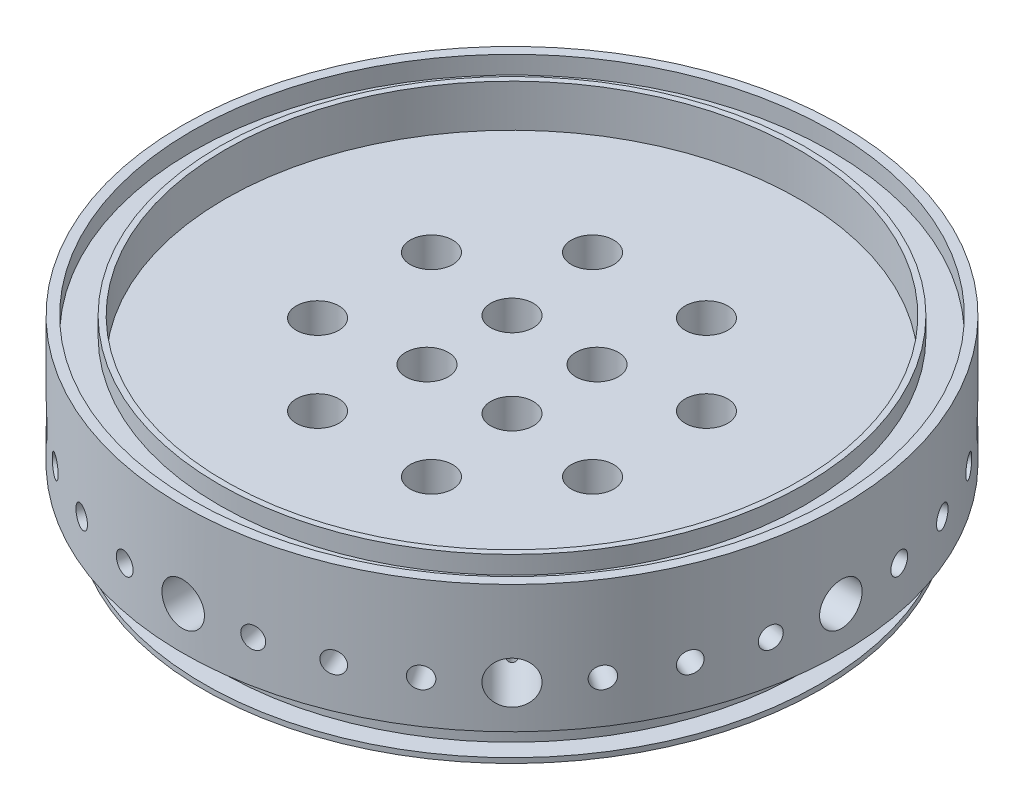
SolidWorks part; units mm, degrees
material "6061-T4 (SS)"
ref_plane "Front Plane" through (0, 0, 0) normal (0, 0, 1) x (1, 0, 0)
ref_plane "Top Plane" through (0, 0, 0) normal (0, 1, 0) x (1, 0, 0)
ref_plane "Right Plane" through (0, 0, 0) normal (1, 0, 0) x (0, 0, -1)
ref_axis "Axis1" through (0, -42.3, 0) along (0, 1, 0)
sketch "Sketch1" plane through (0, 0, 0) normal (0, 0, 1) x (1, 0, 0)
  line L0 (0, 0) -> (-46.0375, 0)
  line L1 (-46.0375, 0) -> (-46.0375, 0.7556)
  line L2 (-46.0375, 0.7556) -> (-43.2181, 0.7556)
  line L3 (-43.2181, 0.7556) -> (-43.2181, 5.5562)
  line L4 (-43.2181, 5.5562) -> (-46.0375, 5.5562)
  line L5 (-46.0375, 5.5562) -> (-46.0375, 6.35)
  line L6 (-46.0375, 6.35) -> (-49.2125, 6.35)
  line L7 (-49.2125, 6.35) -> (-49.2125, 25.4)
  line L10 (-42.8625, 19.05) -> (0, 19.05)
  line L11 (0, 19.05) -> (0, 0)
  line L12 (-42.8625, 19.05) -> (-42.8625, 25.4)
  line L15 (-49.2125, 25.4) -> (-47.7774, 25.4)
  line L16 (-47.7774, 25.4) -> (-47.7774, 22.7076)
  line L17 (-47.7774, 22.7076) -> (-43.7134, 22.7076)
  line L18 (-43.7134, 22.7076) -> (-43.7134, 25.4)
  line L19 (-43.7134, 25.4) -> (-42.8625, 25.4)
  dimension "D1" = 46.0375
  dimension "D2" = 4.8006
  dimension "D3" = 19.05
  dimension "D4" = 0.7937
  dimension "D6" = 3.175
  dimension "D7" = 6.35
  dimension "D9" = 19.05
  dimension "D10" = 4.064
  dimension "D11" = 2.6924
  dimension "D12" = 6.35
  dimension "o-ring -238" = 47.7774
  dimension "o-ring -" = 43.2181
revolve "Revolve1" add sketch "Sketch1" angle 360 about L11 other way angle 360
ref_plane "Plane1" through (49.2125, 0, 0) normal (1, 0, 0) x (0, 0, -1)
hole_wizard "1/8 (0.125) Diameter Hole2" positions "Sketch36" profile "Sketch37" hole size "1/8" standard "ANSI Inch"
sketch "Sketch36" plane through (49.2125, 0, 0) normal (1, 0, 0) x (0, 0, -1)
  line L0 (0, 13.97) -> (0, -13.97) construction
  point P0 (0, 12.7)
  dimension "D1" = 12.7
sketch "Sketch37" plane through (49.2125, 12.7, 0) normal (0, 1, 0) x (0, 0, -1)
  line L0 (0, 0) -> (0, 13.6539)
  line L1 (0, 13.6539) -> (1.5875, 12.7)
  line L2 (1.5875, 12.7) -> (1.5875, 0)
  line L5 (1.5875, 0) -> (0, 0)
  line L10 (0, 13.6539) -> (-1.5875, 12.7) construction
  line L11 (0, -6.35) -> (0, 107.95) construction
  dimension "Hole Dia." = 3.175
  dimension "Hole Depth" = 12.7
  dimension "Drill Angle" = 118
pattern_circular "CirPattern9" count 32 over 360 about axis through (0, -42.3, 0) along (0, 1, 0) of "1/8 (0.125) Diameter Hole2"
hole_wizard "1/4 (0.25) Diameter Hole1" positions "Sketch12" profile "Sketch13" hole size "1/4" standard "ANSI Inch"
sketch "Sketch12" plane through (49.2125, 0, 0) normal (1, 0, 0) x (0, 0, -1)
  point P0 (0, 12.7)
  dimension "D1" = 12.7
sketch "Sketch13" plane through (49.2125, 12.7, 0) normal (0, 1, 0) x (0, 0, -1)
  line L0 (0, 0) -> (0, 14.6077)
  line L1 (0, 14.6077) -> (3.175, 12.7)
  line L2 (3.175, 12.7) -> (3.175, 0)
  line L5 (3.175, 0) -> (0, 0)
  line L10 (0, 14.6077) -> (-3.175, 12.7) construction
  line L11 (0, -6.35) -> (0, 107.95) construction
  dimension "Hole Dia." = 6.35
  dimension "Hole Depth" = 12.7
  dimension "Drill Angle" = 118
hole_wizard "3/16 (0.1875) Diameter Hole1" positions "Sketch14" profile "Sketch15" hole size "3/16" standard "ANSI Inch"
sketch "Sketch14" plane through (49.2125, 0, 0) normal (1, 0, 0) x (0, 0, -1)
  point P0 (0, 12.7)
sketch "Sketch15" plane through (49.2125, 12.7, 0) normal (0, 1, 0) x (0, 0, -1)
  line L0 (0, 0) -> (0, 33.1808)
  line L1 (0, 33.1808) -> (2.3812, 31.75)
  line L2 (2.3812, 31.75) -> (2.3812, 0)
  line L5 (2.3812, 0) -> (0, 0)
  line L10 (0, 33.1808) -> (-2.3813, 31.75) construction
  line L11 (0, -6.35) -> (0, 107.95) construction
  dimension "Hole Dia." = 4.7625
  dimension "Hole Depth" = 31.75
  dimension "Drill Angle" = 118
hole_wizard "1/8 (0.125) Diameter Hole1" positions "Sketch16" profile "Sketch17" hole size "1/8" standard "ANSI Inch"
sketch "Sketch16" plane through (49.2125, 0, 0) normal (1, 0, 0) x (0, 0, -1)
  point P0 (0, 12.7)
sketch "Sketch17" plane through (49.2125, 12.7, 0) normal (0, 1, 0) x (0, 0, -1)
  line L0 (0, 0) -> (0, 45.4039)
  line L1 (0, 45.4039) -> (1.5875, 44.45)
  line L2 (1.5875, 44.45) -> (1.5875, 0)
  line L5 (1.5875, 0) -> (0, 0)
  line L10 (0, 45.4039) -> (-1.5875, 44.45) construction
  line L11 (0, -6.35) -> (0, 107.95) construction
  dimension "Hole Dia." = 3.175
  dimension "Hole Depth" = 44.45
  dimension "Drill Angle" = 118
pattern_circular "CirPattern1" count 8 over 360 about axis through (0, -42.3, 0) along (0, 1, 0) of "1/4 (0.25) Diameter Hole1"
pattern_circular "CirPattern2" count 8 over 360 about axis through (0, -42.3, 0) along (0, 1, 0) of "3/16 (0.1875) Diameter Hole1"
pattern_circular "CirPattern3" count 4 over 360 about axis through (0, -42.3, 0) along (0, 1, 0) of "1/8 (0.125) Diameter Hole1"
ref_plane "Plane2" through (0, 19.05, 0) normal (0, 1, 0) x (1, 0, 0)
hole_wizard "inner large LOX holes" positions "Sketch19" profile "Sketch20" hole size "1/4" standard "ANSI Inch"
sketch "Sketch19" plane through (0, 19.05, 0) normal (0, 1, 0) x (1, 0, 0)
  line L2 (-6.35, 0) -> (0, 0) construction
  line L4 (-6.35, -6.35) -> (-6.35, 0) construction
  point P0 (-6.35, -6.35)
  dimension "D1" = 6.35
  dimension "D2" = 6.35
sketch "Sketch20" plane through (-6.35, 19.05, 6.35) normal (1, 0, 0) x (0, 0, 1)
  line L0 (0, 0) -> (0, 14.6077)
  line L1 (0, 14.6077) -> (3.175, 12.7)
  line L2 (3.175, 12.7) -> (3.175, 0)
  line L5 (3.175, 0) -> (0, 0)
  line L10 (0, 14.6077) -> (-3.175, 12.7) construction
  line L11 (0, -6.35) -> (0, 107.95) construction
  dimension "Hole Dia." = 6.35
  dimension "Hole Depth" = 12.7
  dimension "Drill Angle" = 118
hole_wizard "outer large LOX hole" positions "Sketch21" profile "Sketch22" hole size "1/4" standard "ANSI Inch"
sketch "Sketch21" plane through (0, 19.05, 0) normal (0, 1, 0) x (1, 0, 0)
  line L0 (-20.5332, -8.5051) -> (0, 0) construction
  line L2 (0, 0) -> (-17.5003, 0) construction
  point P0 (-20.5332, -8.5051)
  dimension "D1" = 22.5
  dimension "D2" = 22.225
sketch "Sketch22" plane through (-20.5332, 19.05, 8.5051) normal (1, 0, 0) x (0, 0, 1)
  line L0 (0, 0) -> (0, 14.6077)
  line L1 (0, 14.6077) -> (3.175, 12.7)
  line L2 (3.175, 12.7) -> (3.175, 0)
  line L5 (3.175, 0) -> (0, 0)
  line L10 (0, 14.6077) -> (-3.175, 12.7) construction
  line L11 (0, -6.35) -> (0, 107.95) construction
  dimension "Hole Dia." = 6.35
  dimension "Hole Depth" = 12.7
  dimension "Drill Angle" = 118
pattern_circular "CirPattern4" count 4 over 360 about axis through (0, -42.3, 0) along (0, 1, 0) of "inner large LOX holes"
pattern_circular "CirPattern5" count 8 over 360 about axis through (0, -42.3, 0) along (0, 1, 0) of "outer large LOX hole"
ref_plane "Plane4" through (-41.275, 0, 0) normal (1, 0, 0) x (0, 0, -1)
ref_axis "Axis4" through (-41.275, 0, -54.1338) along (0, 0, 1)
ref_plane "Plane5" through (-0.3135, -3.5837, 0) normal (0.0872, 0.9962, 0) x (0, 0, 1)
ref_plane "Plane6" through (-0.4519, -5.1651, 0) normal (0.0872, 0.9962, 0) x (0, 0, 1)
hole_wizard "film cooling holes" positions "Sketch25" profile "Sketch26" hole size "#74" standard "ANSI Inch"
sketch "Sketch25" plane through (-0.4519, -5.1651, 0) normal (0.0872, 0.9962, 0) x (0, 0, 1)
  line L0 (0, -41.1179) -> (0, 0) construction
  line L1 (-54.1338, -41.1179) -> (54.1338, -41.1179) construction
  point P0 (0, -41.1179)
sketch "Sketch26" plane through (-41.4134, -1.5815, 0) normal (0, 0, 1) x (0.9962, -0.0872, 0)
  line L0 (0, 0) -> (0, 12.8717)
  line L1 (0, 12.8717) -> (0.2857, 12.7)
  line L2 (0.2857, 12.7) -> (0.2857, 0)
  line L5 (0.2857, 0) -> (0, 0)
  line L10 (0, 12.8717) -> (-0.2858, 12.7) construction
  line L11 (0, -6.35) -> (0, 107.95) construction
  dimension "Hole Dia." = 0.5715
  dimension "Hole Depth" = 12.7
  dimension "Drill Angle" = 118
pattern_circular "CirPattern6" count 32 over 360 about axis through (0, -42.3, 0) along (0, 1, 0) of "film cooling holes"
hole_wizard "3/64 (0.04688) Diameter Hole1" positions "Sketch38" profile "Sketch39" hole size "3/64" standard "ANSI Inch"
sketch "Sketch38" plane through (-0.4519, -5.1651, 0) normal (0.0872, 0.9962, 0) x (0, 0, 1)
  point P0 (0, -41.1179)
sketch "Sketch39" plane through (-41.4134, -1.5815, 0) normal (0, 0, 1) x (0.9962, -0.0872, 0)
  line L0 (0, 0) -> (0, 13.0577)
  line L1 (0, 13.0577) -> (0.5954, 12.7)
  line L2 (0.5954, 12.7) -> (0.5954, 0)
  line L5 (0.5954, 0) -> (0, 0)
  line L10 (0, 13.0577) -> (-0.5954, 12.7) construction
  line L11 (0, -6.35) -> (0, 107.95) construction
  dimension "Hole Dia." = 1.1908
  dimension "Hole Depth" = 12.7
  dimension "Drill Angle" = 118
pattern_circular "CirPattern10" count 8 over 360 about axis through (0, -42.3, 0) along (0, 1, 0) of "3/64 (0.04688) Diameter Hole1"
hole_wizard "1/16 (0.0625) Diameter Hole2" positions "Sketch27" profile "Sketch28" hole size "1/16" standard "ANSI Inch"
sketch "Sketch27" plane through (0, 0, 0) normal (0, 1, 0) x (1, 0, 0)
  point P0 (-6.35, 0)
  dimension "D1" = 6.35
sketch "Sketch28" plane through (-6.35, 0, 0) normal (1, 0, 0) x (0, 0, -1)
  line L0 (0, 0) -> (0, 13.1769)
  line L1 (0, 13.1769) -> (0.7937, 12.7)
  line L2 (0.7937, 12.7) -> (0.7937, 0)
  line L5 (0.7937, 0) -> (0, 0)
  line L10 (0, 13.1769) -> (-0.7938, 12.7) construction
  line L11 (0, -6.35) -> (0, 107.95) construction
  dimension "Hole Dia." = 1.5875
  dimension "Hole Depth" = 12.7
  dimension "Drill Angle" = 118
ref_axis "Axis2" through (0, 19.05, -88.99) along (0, 0, 1)
ref_axis "Axis3" through (2.4606, 19.05, 0) along (-1, 0, 0)
ref_plane "impinging plane" through (0, -6.35, 0) normal (0, -1, 0) x (-1, 0, 0)
ref_axis "Axis5" through (-53.7659, -6.35, 0) along (1, 0, 0)
ref_plane "Plane8" through (0, -4.7625, -2.7496) normal (0, -0.866, -0.5) x (1, 0, 0)
hole_wizard "1/16 (0.0625) Diameter Hole1" positions "Sketch31" profile "Sketch30" hole size "1/16" standard "ANSI Inch"
sketch "Sketch31" plane through (0, -4.7625, -2.7496) normal (0, -0.866, -0.5) x (1, 0, 0)
  line L0 (-53.7659, 3.175) -> (54.5016, 3.175) construction
  point P0 (-6.35, 3.175)
  dimension "D1" = 6.35
sketch "Sketch30" plane through (-6.35, -6.35, 0) normal (1, 0, 0) x (0, 0.5, -0.866)
  line L0 (0, 0) -> (0, 16.0979)
  line L1 (0, 16.0979) -> (0.7937, 15.621)
  line L2 (0.7937, 15.621) -> (0.7937, 0)
  line L5 (0.7937, 0) -> (0, 0)
  line L10 (0, 16.0979) -> (-0.7938, 15.621) construction
  line L11 (0, -6.35) -> (0, 107.95) construction
  dimension "Hole Dia." = 1.5875
  dimension "Hole Depth" = 15.621
  dimension "Drill Angle" = 118
hole_wizard "1/16 (0.0625) Diameter Hole3" positions "Sketch32" profile "Sketch33" hole size "1/16" standard "ANSI Inch"
sketch "Sketch32" plane through (0, 0, 0) normal (0, 1, 0) x (1, 0, 0)
  point P0 (-22.225, 0)
  dimension "D1" = 22.225
sketch "Sketch33" plane through (-22.225, 0, 0) normal (1, 0, 0) x (0, 0, -1)
  line L0 (0, 0) -> (0, 13.1769)
  line L1 (0, 13.1769) -> (0.7937, 12.7)
  line L2 (0.7937, 12.7) -> (0.7937, 0)
  line L5 (0.7937, 0) -> (0, 0)
  line L10 (0, 13.1769) -> (-0.7938, 12.7) construction
  line L11 (0, -6.35) -> (0, 107.95) construction
  dimension "Hole Dia." = 1.5875
  dimension "Hole Depth" = 12.7
  dimension "Drill Angle" = 118
hole_wizard "1/16 (0.0625) Diameter Hole4" positions "Sketch34" profile "Sketch35" hole size "1/16" standard "ANSI Inch"
sketch "Sketch34" plane through (0, -4.7625, -2.7496) normal (0, -0.866, -0.5) x (1, 0, 0)
  line L0 (-53.7659, 3.175) -> (54.5016, 3.175) construction
  point P0 (-22.225, 3.175)
  dimension "D1" = 22.225
sketch "Sketch35" plane through (-22.225, -6.35, 0) normal (1, 0, 0) x (0, 0.5, -0.866)
  line L0 (0, 0) -> (0, 19.5269)
  line L1 (0, 19.5269) -> (0.7937, 19.05)
  line L2 (0.7937, 19.05) -> (0.7937, 0)
  line L5 (0.7937, 0) -> (0, 0)
  line L10 (0, 19.5269) -> (-0.7938, 19.05) construction
  line L11 (0, -6.35) -> (0, 107.95) construction
  dimension "Hole Dia." = 1.5875
  dimension "Hole Depth" = 19.05
  dimension "Drill Angle" = 118
mirror "Mirror1" about plane through (0, 0, 0) normal (0, 0, 1) of "1/16 (0.0625) Diameter Hole1"
mirror "Mirror2" about plane through (0, 0, 0) normal (0, 0, 1) of "1/16 (0.0625) Diameter Hole4"
pattern_circular "CirPattern7" count 4 over 360 about axis through (0, -42.3, 0) along (0, 1, 0) of "1/16 (0.0625) Diameter Hole1", "Mirror1", "1/16 (0.0625) Diameter Hole2"
pattern_circular "CirPattern8" count 8 over 360 about axis through (0, -42.3, 0) along (0, 1, 0) of "Mirror2", "1/16 (0.0625) Diameter Hole4", "1/16 (0.0625) Diameter Hole3"
